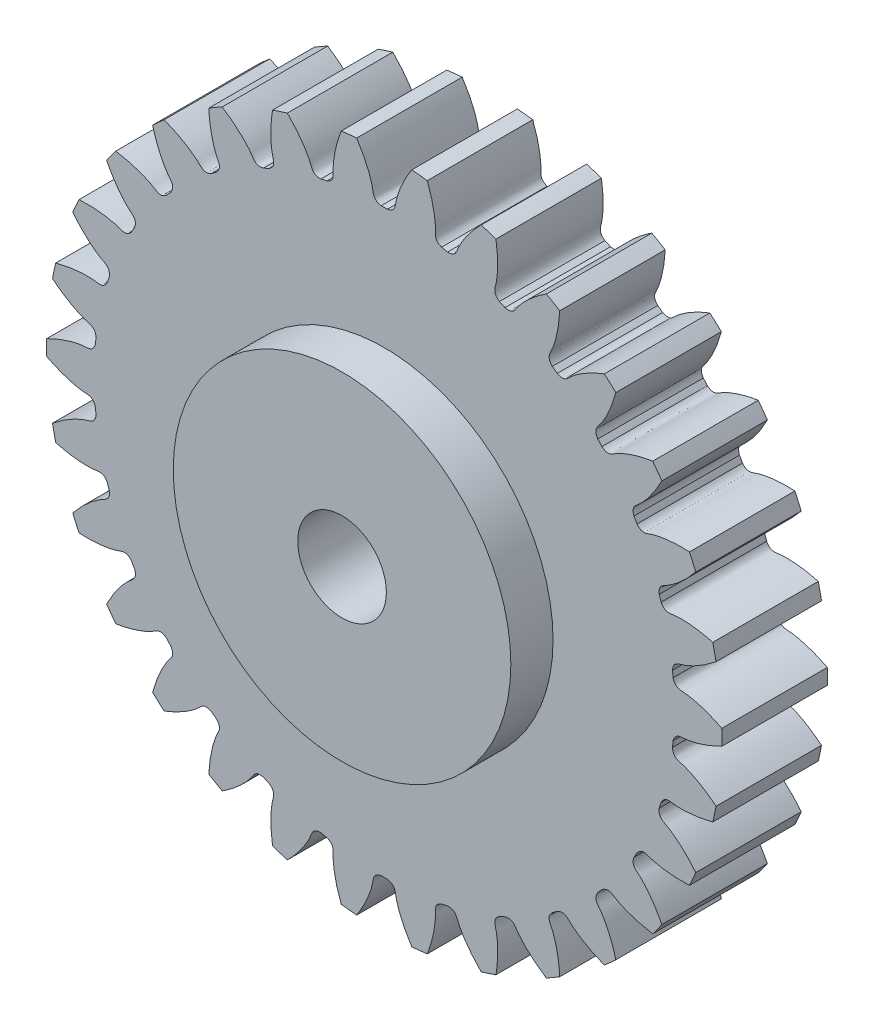
SolidWorks part; units mm, degrees
ref_plane "前视基准面" through (0, 0, 0) normal (0, 0, 1) x (1, 0, 0)
ref_plane "上视基准面" through (0, 0, 0) normal (0, 1, 0) x (1, 0, 0)
ref_plane "右视基准面" through (0, 0, 0) normal (1, 0, 0) x (0, 0, -1)
sketch "草图1" plane through (0, 0, 0) normal (0, 0, 1) x (1, 0, 0)
  circle A0 centre (0, 0) radius 8
extrude "凸台-拉伸1" add sketch "草图1" along normal blind 2.5
ref_axis "基准轴1" through (0, 0, -0.15) along (0, 0, 1)
sketch "草图2" plane through (0, 0, 0) normal (0, 0, 1) x (1, 0, 0)
  line L0 (0, 0) -> (0, 8) construction
  circle A0 centre (0, 0) radius 8 construction
  arc A1 (0.0728, 6.8746) -> (-0.0728, 6.8746) centre (0, 0) ccw
  arc A2 (1.6832, 9.0953) -> (-1.6832, 9.0953) centre (0, 0) ccw
  spline S0 degree 3 poles (0.0728, 6.8746) (0.2541, 6.9065) (0.2552, 7.0236) (0.2795, 7.1443) (0.285, 7.1691) (0.2916, 7.1965) (0.2995, 7.2264) (0.3088, 7.259) (0.3196, 7.294) (0.3319, 7.3315) (0.3459, 7.3714) (0.3617, 7.4137) (0.3794, 7.4582) (0.3991, 7.505) (0.4208, 7.554) (0.4447, 7.605) (0.4709, 7.6581) (0.4994, 7.7132) (0.5303, 7.7702) (0.5638, 7.829) (0.5999, 7.8895) (0.6387, 7.9517) (0.6803, 8.0155) (0.7247, 8.0807) (0.772, 8.1474) (0.8224, 8.2154) (0.8758, 8.2845) (0.9324, 8.3548) (0.9921, 8.4261) (1.0552, 8.4983) (1.1215, 8.5713) (1.1913, 8.6451) (1.2645, 8.7194) (1.3411, 8.7942) (1.4213, 8.8694) (1.5345, 8.9713) (1.6227, 9.046) (1.6832, 9.0953) knots 0 0 0 0 0.115324 0.123413 0.132512 0.142623 0.153745 0.165878 0.179022 0.193177 0.208343 0.22452 0.241708 0.259907 0.279117 0.299338 0.320571 0.342814 0.366068 0.390334 0.41561 0.441898 0.469196 0.497506 0.526827 0.557158 0.588501 0.620855 0.65422 0.688595 0.723982 0.76038 0.797789 0.836209 0.87564 0.916083 1 1 1 1
  spline S1 degree 3 poles (-0.0728, 6.8746) (-0.2541, 6.9065) (-0.2552, 7.0236) (-0.2795, 7.1443) (-0.285, 7.1691) (-0.2916, 7.1965) (-0.2995, 7.2264) (-0.3088, 7.259) (-0.3196, 7.294) (-0.3319, 7.3315) (-0.3459, 7.3714) (-0.3617, 7.4137) (-0.3794, 7.4582) (-0.3991, 7.505) (-0.4208, 7.554) (-0.4447, 7.605) (-0.4709, 7.6581) (-0.4994, 7.7132) (-0.5303, 7.7702) (-0.5638, 7.829) (-0.5999, 7.8895) (-0.6387, 7.9517) (-0.6803, 8.0155) (-0.7247, 8.0807) (-0.772, 8.1474) (-0.8224, 8.2154) (-0.8758, 8.2845) (-0.9324, 8.3548) (-0.9921, 8.4261) (-1.0552, 8.4983) (-1.1215, 8.5713) (-1.1913, 8.6451) (-1.2645, 8.7194) (-1.3411, 8.7942) (-1.4213, 8.8694) (-1.5345, 8.9713) (-1.6227, 9.046) (-1.6832, 9.0953) knots 0 0 0 0 0.115324 0.123413 0.132512 0.142623 0.153745 0.165878 0.179022 0.193177 0.208343 0.22452 0.241708 0.259907 0.279117 0.299338 0.320571 0.342814 0.366068 0.390334 0.41561 0.441898 0.469196 0.497506 0.526827 0.557158 0.588501 0.620855 0.65422 0.688595 0.723982 0.76038 0.797789 0.836209 0.87564 0.916083 1 1 1 1
extrude "切除-拉伸1" cut sketch "草图2" along normal through all
pattern_circular "阵列(圆周)1" count 30 every 12 about axis through (0, 0, -0.15) along (0, 0, 1) of "切除-拉伸1"
sketch "草图3" plane through (0, 0, 0) normal (0, 0, 1) x (1, 0, 0)
  circle A0 centre (0, 0) radius 7.5 construction
  dimension "Dn" = 15
sketch "草图5" plane through (0, 0, 0) normal (0, 0, -1) x (-1, 0, 0)
  circle A0 centre (0, 0) radius 4
  dimension "D1" = 8
extrude "凸台-拉伸2" add sketch "草图5" along normal blind 1
sketch "草图6" plane through (0, 0, 2.5) normal (0, 0, 1) x (1, 0, 0)
  circle A0 centre (0, 0) radius 4
  dimension "D1" = 8
extrude "凸台-拉伸3" add sketch "草图6" along normal blind 1
sketch "草图4" plane through (0, 0, 0) normal (0, 0, -1) x (-1, 0, 0)
  line L0 (0, 0) -> (0, 0.5383) construction
  arc A0 (-0.525, 0.9093) -> (0.525, 0.9093) centre (0, 0) ccw
  arc A1 (-0.525, 0.9093) -> (0.525, 0.9093) centre (0, 0) cw
  dimension "D1" = 2.1
extrude "切除-拉伸2" cut sketch "草图4" along normal up to next from surface starting at face at (4, 0, 3.5)
